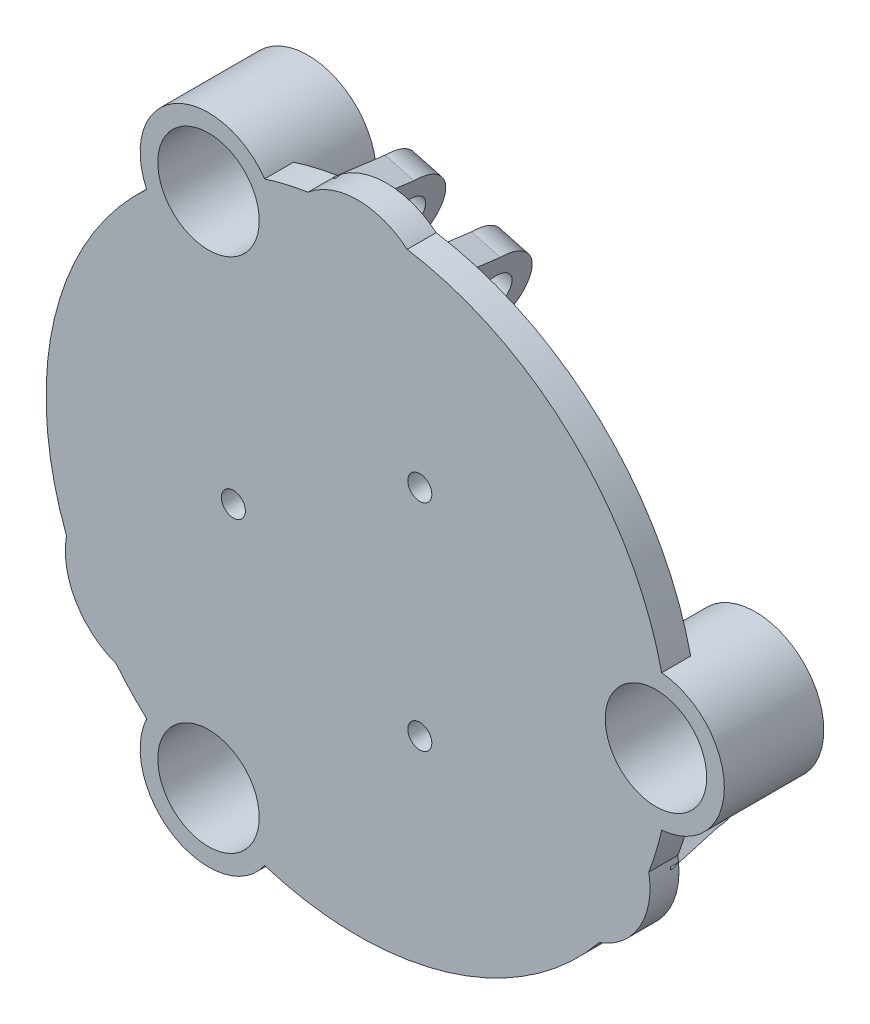
SolidWorks part; units mm, degrees
ref_plane "Front Plane" through (0, 0, 0) normal (0, 0, 1) x (1, 0, 0)
ref_plane "Top Plane" through (0, 0, 0) normal (0, 1, 0) x (1, 0, 0)
ref_plane "Right Plane" through (0, 0, 0) normal (1, 0, 0) x (0, 0, -1)
sketch "S01 - Joining centre of floating Y" plane through (0, 0, 0) normal (0, 0, 1) x (1, 0, 0)
  circle A0 centre (0, 0) radius 9
  dimension "D1" = 18
extrude "01 - Joining centre of floating Y" add sketch "S01 - Joining centre of floating Y" along normal blind 3.5 from offset 33.5
sketch "S02 - Floating spoke 1" plane through (0, 0, 0) normal (0, 0, 1) x (1, 0, 0)
  line L0 (4.65, -8.054) -> (-21.3308, -23.054)
  line L1 (-30.6308, -6.946) -> (-4.65, 8.054)
  arc A0 (-21.3308, -23.054) -> (-30.6308, -6.946) centre (-25.9808, -15) cw
  arc A1 (-4.65, 8.054) -> (4.65, -8.054) centre (0, 0) cw
  dimension "D1" = 9.3
  dimension "D2" = 9.3
  dimension "D3" = 4.65
  dimension "D4" = 4.65
  dimension "D5" = 21.3308
  dimension "D6" = 25.9808
  dimension "D7" = 30.6308
  dimension "D8" = 6.946
extrude "02 - Floating spoke 1" add sketch "S02 - Floating spoke 1" along normal blind 3.5 from offset 33.5
sketch "S03 - Floating spoke 2" plane through (0, 0, 0) normal (0, 0, 1) x (1, 0, 0)
  line L0 (4.65, 8.054) -> (30.6308, -6.946)
  line L1 (21.3308, -23.054) -> (-4.65, -8.054)
  arc A0 (30.6308, -6.946) -> (21.3308, -23.054) centre (25.9808, -15) cw
  arc A1 (-4.65, -8.054) -> (4.65, 8.054) centre (0, 0) cw
  dimension "D1" = 9.3
  dimension "D2" = 9.3
  dimension "D3" = 4.65
  dimension "D4" = 21.3308
  dimension "D5" = 25.9808
  dimension "D6" = 30.6308
  dimension "D7" = 4.65
  dimension "D8" = 6.946
extrude "03 - Floating spoke 2" add sketch "S03 - Floating spoke 2" along normal blind 3.5 from offset 33.5
sketch "S04 - Floating spoke 3" plane through (0, 0, 0) normal (0, 0, 1) x (1, 0, 0)
  line L0 (-9.3, 0) -> (-9.3, 30)
  line L1 (9.3, 30) -> (9.3, 0)
  arc A0 (-9.3, 30) -> (9.3, 30) centre (0, 30) cw
  arc A1 (9.3, 0) -> (-9.3, 0) centre (0, 0) cw
  dimension "D1" = 9.3
  dimension "D2" = 30
extrude "04 - Floating spoke 3" add sketch "S04 - Floating spoke 3" along normal blind 3.5 from offset 33.5
sketch "S05 - Moving tendon tie web 1" plane through (0, 0, 0) normal (0, 0, 1) x (1, 0, 0)
  line L0 (25.2997, -21.2631) -> (6.8189, -19.2535)
  line L1 (8.1811, -6.7273) -> (26.6618, -8.7369)
  arc A0 (6.8189, -19.2535) -> (8.1811, -6.7273) centre (7.5, -12.9904) cw
  arc A1 (26.6618, -8.7369) -> (25.2997, -21.2631) centre (25.9808, -15) cw
  dimension "D1" = 6.3
  dimension "D2" = 6.3
  dimension "D3" = 6.8189
  dimension "D4" = 7.5
  dimension "D5" = 8.1811
  dimension "D6" = 25.2997
  dimension "D7" = 25.9808
  dimension "D8" = 26.6618
  dimension "D9" = 6.7273
  dimension "D10" = 8.7369
extrude "05 - Moving tendon tie web 1" add sketch "S05 - Moving tendon tie web 1" along normal blind 3.5 from offset 33.5
sketch "S06 - Tendon anchor base 1" plane through (0, 0, 0) normal (0, 0, 1) x (1, 0, 0)
  circle A0 centre (7.5, -12.9904) radius 4.2
  dimension "D1" = 8.4
  dimension "D2" = 7.5
  dimension "D3" = 12.9904
extrude "06 - Tendon anchor base 1" add sketch "S06 - Tendon anchor base 1" along normal blind 3.7 from offset 29.8
sketch "S07 - Tendon mouth 1" plane through (0, 0, 0) normal (0, 0, 1) x (1, 0, 0)
  circle A0 centre (7.5, -12.9904) radius 3.15
  dimension "D1" = 6.3
  dimension "D2" = 7.5
  dimension "D3" = 12.9904
extrude "07 - Tendon mouth 1" add sketch "S07 - Tendon mouth 1" along normal blind 1.8 from offset 28
sketch "S08 - Moving tendon tie web 2" plane through (0, 0, 0) normal (0, 0, 1) x (1, 0, 0)
  line L0 (5.7645, 32.5417) -> (13.2645, 15.5321)
  line L1 (1.7355, 10.4487) -> (-5.7645, 27.4583)
  arc A0 (13.2645, 15.5321) -> (1.7355, 10.4487) centre (7.5, 12.9904) cw
  arc A1 (-5.7645, 27.4583) -> (5.7645, 32.5417) centre (0, 30) cw
  dimension "D1" = 6.3
  dimension "D2" = 6.3
  dimension "D3" = 1.7355
  dimension "D4" = 5.7645
  dimension "D5" = 7.5
  dimension "D6" = 13.2645
  dimension "D7" = 5.7645
  dimension "D8" = 10.4487
  dimension "D9" = 27.4583
extrude "08 - Moving tendon tie web 2" add sketch "S08 - Moving tendon tie web 2" along normal blind 3.5 from offset 33.5
sketch "S09 - Tendon anchor base 2" plane through (0, 0, 0) normal (0, 0, 1) x (1, 0, 0)
  circle A0 centre (7.5, 12.9904) radius 4.2
  dimension "D1" = 8.4
  dimension "D2" = 7.5
  dimension "D3" = 12.9904
extrude "09 - Tendon anchor base 2" add sketch "S09 - Tendon anchor base 2" along normal blind 3.7 from offset 29.8
sketch "S10 - Tendon mouth 2" plane through (0, 0, 0) normal (0, 0, 1) x (1, 0, 0)
  circle A0 centre (7.5, 12.9904) radius 3.15
  dimension "D1" = 6.3
  dimension "D2" = 7.5
  dimension "D3" = 12.9904
extrude "10 - Tendon mouth 2" add sketch "S10 - Tendon mouth 2" along normal blind 1.8 from offset 28
sketch "S11 - Moving tendon tie web 3" plane through (0, 0, 0) normal (0, 0, 1) x (1, 0, 0)
  line L0 (-31.0642, -11.2786) -> (-20.0835, 3.7214)
  line L1 (-9.9165, -3.7214) -> (-20.8973, -18.7214)
  arc A0 (-20.0835, 3.7214) -> (-9.9165, -3.7214) centre (-15, 0) cw
  arc A1 (-20.8973, -18.7214) -> (-31.0642, -11.2786) centre (-25.9808, -15) cw
  dimension "D1" = 6.3
  dimension "D2" = 6.3
  dimension "D3" = 9.9165
  dimension "D4" = 15
  dimension "D5" = 20.0835
  dimension "D6" = 20.8973
  dimension "D7" = 25.9808
  dimension "D8" = 31.0642
  dimension "D9" = 11.2786
extrude "11 - Moving tendon tie web 3" add sketch "S11 - Moving tendon tie web 3" along normal blind 3.5 from offset 33.5
sketch "S12 - Tendon anchor base 3" plane through (0, 0, 0) normal (0, 0, 1) x (1, 0, 0)
  circle A0 centre (-15, 0) radius 4.2
  dimension "D1" = 8.4
  dimension "D2" = 15
extrude "12 - Tendon anchor base 3" add sketch "S12 - Tendon anchor base 3" along normal blind 3.7 from offset 29.8
sketch "S13 - Tendon mouth 3" plane through (0, 0, 0) normal (0, 0, 1) x (1, 0, 0)
  circle A0 centre (-15, 0) radius 3.15
  dimension "D1" = 6.3
  dimension "D2" = 15
extrude "13 - Tendon mouth 3" add sketch "S13 - Tendon mouth 3" along normal blind 1.8 from offset 28
sketch "S14 - Joined drive hoop" plane through (0, 0, 0) normal (0, 0, 1) x (1, 0, 0)
  circle A0 centre (0, 0) radius 37.6
  dimension "D2" = 75.2
extrude "14 - Joined drive hoop" add sketch "S14 - Joined drive hoop" along normal blind 3.5 from offset 33.5
sketch "S15 - Sliding guide barrel 1" plane through (0, 0, 0) normal (0, 0, 1) x (1, 0, 0)
  circle A0 centre (36, 0) radius 8.25
  dimension "D1" = 16.5
  dimension "D2" = 36
extrude "15 - Sliding guide barrel 1" add sketch "S15 - Sliding guide barrel 1" along normal blind 12 from offset 25
sketch "S16 - Sliding guide barrel 2" plane through (0, 0, 0) normal (0, 0, 1) x (1, 0, 0)
  circle A0 centre (-18, 31.1769) radius 8.25
  dimension "D1" = 16.5
  dimension "D2" = 18
  dimension "D3" = 31.1769
extrude "16 - Sliding guide barrel 2" add sketch "S16 - Sliding guide barrel 2" along normal blind 12 from offset 25
sketch "S17 - Sliding guide barrel 3" plane through (0, 0, 0) normal (0, 0, 1) x (1, 0, 0)
  circle A0 centre (-18, -31.1769) radius 8.25
  dimension "D1" = 16.5
  dimension "D2" = 18
  dimension "D3" = 31.1769
extrude "17 - Sliding guide barrel 3" add sketch "S17 - Sliding guide barrel 3" along normal blind 12 from offset 25
sketch "S18 - Guide bushing seats" plane through (0, 0, 0) normal (0, 0, 1) x (1, 0, 0)
  circle A0 centre (36, 0) radius 6.12
  circle A1 centre (-18, 31.1769) radius 6.12
  circle A2 centre (-18, -31.1769) radius 6.12
  dimension "D1" = 12.24
  dimension "D2" = 12.24
  dimension "D3" = 12.24
  dimension "D4" = 36
  dimension "D5" = 18
  dimension "D6" = 31.1769
  dimension "D7" = 31.1769
extrude "18 - Guide bushing seats" cut sketch "S18 - Guide bushing seats" along normal blind 14 from offset 24
sketch "S19 - Through tendon tie eyes" plane through (0, 0, 0) normal (0, 0, 1) x (1, 0, 0)
  circle A0 centre (7.5, -12.9904) radius 1.45
  circle A1 centre (7.5, 12.9904) radius 1.45
  circle A2 centre (-15, 0) radius 1.45
  dimension "D1" = 2.9
  dimension "D2" = 2.9
  dimension "D3" = 2.9
  dimension "D4" = 7.5
  dimension "D5" = 15
  dimension "D6" = 12.9904
  dimension "D7" = 12.9904
extrude "19 - Through tendon tie eyes" cut sketch "S19 - Through tendon tie eyes" along normal blind 10 from offset 27.8
sketch3d "Plane points - Integral B1 fork cheek L"
  point P0 (-25.9808, -15, 28)
  point P1 (-8.5941, -10.3413, 28)
  point P2 (-25.9808, -15, 10)
ref_plane "Drilling plane - Integral B1 fork cheek L" through (2.0096, -7.5, 0) normal (-0.2588, 0.9659, 0) x (0.9659, 0.2588, 0)
sketch "S20 - Integral B1 fork cheek L" plane through (2.0096, -7.5, 0) normal (-0.2588, 0.9659, 0) x (0.9659, 0.2588, 0)
  line L0 (-35.0778, -34.5) -> (-22.8778, -34.5)
  line L1 (-22.8778, -34.5) -> (-24.0278, -28)
  line L2 (-33.9278, -28) -> (-35.0778, -34.5)
  arc A0 (-24.0278, -28) -> (-33.9278, -28) centre (-28.9778, -28) ccw
  dimension "D1" = 4.95
  dimension "D2" = 22.8778
  dimension "D3" = 28.9778
  dimension "D4" = 35.0778
  dimension "D5" = 28
  dimension "D6" = 34.5
extrude "20 - Integral B1 fork cheek L" add sketch "S20 - Integral B1 fork cheek L" along normal blind 3.6 from offset 7.2 offset against normal yes
sketch3d "Plane points - Integral B1 fork cheek R"
  point P0 (-25.9808, -15, 28)
  point P1 (-8.5941, -10.3413, 28)
  point P2 (-25.9808, -15, 10)
ref_plane "Drilling plane - Integral B1 fork cheek R" through (2.0096, -7.5, 0) normal (-0.2588, 0.9659, 0) x (0.9659, 0.2588, 0)
sketch "S21 - Integral B1 fork cheek R" plane through (2.0096, -7.5, 0) normal (-0.2588, 0.9659, 0) x (0.9659, 0.2588, 0)
  line L0 (-35.0778, -34.5) -> (-22.8778, -34.5)
  line L1 (-22.8778, -34.5) -> (-24.0278, -28)
  line L2 (-33.9278, -28) -> (-35.0778, -34.5)
  arc A0 (-24.0278, -28) -> (-33.9278, -28) centre (-28.9778, -28) ccw
  dimension "D1" = 4.95
  dimension "D2" = 22.8778
  dimension "D3" = 28.9778
  dimension "D4" = 35.0778
  dimension "D5" = 28
  dimension "D6" = 34.5
extrude "21 - Integral B1 fork cheek R" add sketch "S21 - Integral B1 fork cheek R" along normal blind 3.6 from offset 3.6
sketch3d "Plane points - B1 pivot through both cheeks"
  point P0 (-25.9808, -15, 28)
  point P1 (-8.5941, -10.3413, 28)
  point P2 (-25.9808, -15, 10)
ref_plane "Drilling plane - B1 pivot through both cheeks" through (2.0096, -7.5, 0) normal (-0.2588, 0.9659, 0) x (0.9659, 0.2588, 0)
sketch "S22 - B1 pivot through both cheeks" plane through (2.0096, -7.5, 0) normal (-0.2588, 0.9659, 0) x (0.9659, 0.2588, 0)
  circle A0 centre (-28.9778, -28) radius 1.65
  dimension "D1" = 3.3
  dimension "D2" = 28.9778
  dimension "D3" = 28
extrude "22 - B1 pivot through both cheeks" cut sketch "S22 - B1 pivot through both cheeks" along normal blind 15 from offset 7.5 offset against normal yes
sketch3d "Plane points - B1 recessed pivot screw head"
  point P0 (-25.9808, -15, 28)
  point P1 (-8.5941, -10.3413, 28)
  point P2 (-25.9808, -15, 10)
ref_plane "Drilling plane - B1 recessed pivot screw head" through (2.0096, -7.5, 0) normal (-0.2588, 0.9659, 0) x (0.9659, 0.2588, 0)
sketch "S23 - B1 recessed pivot screw head" plane through (2.0096, -7.5, 0) normal (-0.2588, 0.9659, 0) x (0.9659, 0.2588, 0)
  circle A0 centre (-28.9778, -28) radius 2.7
  dimension "D1" = 5.4
  dimension "D2" = 28.9778
  dimension "D3" = 28
extrude "23 - B1 recessed pivot screw head" cut sketch "S23 - B1 recessed pivot screw head" along normal blind 1.5 from offset 7.3 offset against normal yes
sketch3d "Plane points - Integral B2 fork cheek L"
  point P0 (25.9808, -15, 28)
  point P1 (13.2528, -2.2721, 28)
  point P2 (25.9808, -15, 10)
ref_plane "Drilling plane - Integral B2 fork cheek L" through (5.4904, 5.4904, 0) normal (-0.7071, -0.7071, 0) x (0, 0, 1)
sketch "S24 - Integral B2 fork cheek L" plane through (5.4904, 5.4904, 0) normal (-0.7071, -0.7071, 0) x (0, 0, 1)
  line L0 (34.5, -35.0778) -> (34.5, -22.8778)
  line L1 (34.5, -22.8778) -> (28, -24.0278)
  line L2 (28, -33.9278) -> (34.5, -35.0778)
  arc A0 (28, -24.0278) -> (28, -33.9278) centre (28, -28.9778) ccw
  dimension "D1" = 4.95
  dimension "D2" = 28
  dimension "D3" = 34.5
  dimension "D4" = 22.8778
  dimension "D5" = 28.9778
  dimension "D6" = 35.0778
extrude "24 - Integral B2 fork cheek L" add sketch "S24 - Integral B2 fork cheek L" along normal blind 3.6 from offset 7.2 offset against normal yes
sketch3d "Plane points - Integral B2 fork cheek R"
  point P0 (25.9808, -15, 28)
  point P1 (13.2528, -2.2721, 28)
  point P2 (25.9808, -15, 10)
ref_plane "Drilling plane - Integral B2 fork cheek R" through (5.4904, 5.4904, 0) normal (-0.7071, -0.7071, 0) x (0, 0, 1)
sketch "S25 - Integral B2 fork cheek R" plane through (5.4904, 5.4904, 0) normal (-0.7071, -0.7071, 0) x (0, 0, 1)
  line L0 (34.5, -35.0778) -> (34.5, -22.8778)
  line L1 (34.5, -22.8778) -> (28, -24.0278)
  line L2 (28, -33.9278) -> (34.5, -35.0778)
  arc A0 (28, -24.0278) -> (28, -33.9278) centre (28, -28.9778) ccw
  dimension "D1" = 4.95
  dimension "D2" = 28
  dimension "D3" = 34.5
  dimension "D4" = 22.8778
  dimension "D5" = 28.9778
  dimension "D6" = 35.0778
extrude "25 - Integral B2 fork cheek R" add sketch "S25 - Integral B2 fork cheek R" along normal blind 3.6 from offset 3.6
sketch3d "Plane points - B2 pivot through both cheeks"
  point P0 (25.9808, -15, 28)
  point P1 (13.2528, -2.2721, 28)
  point P2 (25.9808, -15, 10)
ref_plane "Drilling plane - B2 pivot through both cheeks" through (5.4904, 5.4904, 0) normal (-0.7071, -0.7071, 0) x (0, 0, 1)
sketch "S26 - B2 pivot through both cheeks" plane through (5.4904, 5.4904, 0) normal (-0.7071, -0.7071, 0) x (0, 0, 1)
  circle A0 centre (28, -28.9778) radius 2.6
  dimension "D1" = 5.2
  dimension "D2" = 28
  dimension "D3" = 28.9778
extrude "26 - B2 pivot through both cheeks" cut sketch "S26 - B2 pivot through both cheeks" along normal blind 15 from offset 7.5 offset against normal yes
sketch3d "Plane points - B2 recessed pivot screw head"
  point P0 (25.9808, -15, 28)
  point P1 (13.2528, -2.2721, 28)
  point P2 (25.9808, -15, 10)
ref_plane "Drilling plane - B2 recessed pivot screw head" through (5.4904, 5.4904, 0) normal (-0.7071, -0.7071, 0) x (0, 0, 1)
sketch "S27 - B2 recessed pivot screw head" plane through (5.4904, 5.4904, 0) normal (-0.7071, -0.7071, 0) x (0, 0, 1)
  circle A0 centre (28, -28.9778) radius 2.7
  dimension "D1" = 5.4
  dimension "D2" = 28
  dimension "D3" = 28.9778
extrude "27 - B2 recessed pivot screw head" cut sketch "S27 - B2 recessed pivot screw head" along normal blind 1.5 from offset 7.3 offset against normal yes
sketch3d "Plane points - Integral B3 fork cheek L"
  point P0 (0, 30, 28)
  point P1 (-4.6587, 12.6133, 28)
  point P2 (0, 30, 10)
ref_plane "Drilling plane - Integral B3 fork cheek L" through (-7.5, 2.0096, 0) normal (0.9659, -0.2588, 0) x (0, 0, -1)
sketch "S28 - Integral B3 fork cheek L" plane through (-7.5, 2.0096, 0) normal (0.9659, -0.2588, 0) x (0, 0, -1)
  line L0 (-34.5, 35.0778) -> (-34.5, 22.8778)
  line L1 (-34.5, 22.8778) -> (-28, 24.0278)
  line L2 (-28, 33.9278) -> (-34.5, 35.0778)
  arc A0 (-28, 24.0278) -> (-28, 33.9278) centre (-28, 28.9778) ccw
  dimension "D1" = 4.95
  dimension "D2" = 28
  dimension "D3" = 34.5
  dimension "D4" = 22.8778
  dimension "D5" = 28.9778
  dimension "D6" = 35.0778
extrude "28 - Integral B3 fork cheek L" add sketch "S28 - Integral B3 fork cheek L" along normal blind 3.6 from offset 7.2 offset against normal yes
sketch3d "Plane points - Integral B3 fork cheek R"
  point P0 (0, 30, 28)
  point P1 (-4.6587, 12.6133, 28)
  point P2 (0, 30, 10)
ref_plane "Drilling plane - Integral B3 fork cheek R" through (-7.5, 2.0096, 0) normal (0.9659, -0.2588, 0) x (0, 0, -1)
sketch "S29 - Integral B3 fork cheek R" plane through (-7.5, 2.0096, 0) normal (0.9659, -0.2588, 0) x (0, 0, -1)
  line L0 (-34.5, 35.0778) -> (-34.5, 22.8778)
  line L1 (-34.5, 22.8778) -> (-28, 24.0278)
  line L2 (-28, 33.9278) -> (-34.5, 35.0778)
  arc A0 (-28, 24.0278) -> (-28, 33.9278) centre (-28, 28.9778) ccw
  dimension "D1" = 4.95
  dimension "D2" = 28
  dimension "D3" = 34.5
  dimension "D4" = 22.8778
  dimension "D5" = 28.9778
  dimension "D6" = 35.0778
extrude "29 - Integral B3 fork cheek R" add sketch "S29 - Integral B3 fork cheek R" along normal blind 3.6 from offset 3.6
sketch3d "Plane points - B3 pivot through both cheeks"
  point P0 (0, 30, 28)
  point P1 (-4.6587, 12.6133, 28)
  point P2 (0, 30, 10)
ref_plane "Drilling plane - B3 pivot through both cheeks" through (-7.5, 2.0096, 0) normal (0.9659, -0.2588, 0) x (0, 0, -1)
sketch "S30 - B3 pivot through both cheeks" plane through (-7.5, 2.0096, 0) normal (0.9659, -0.2588, 0) x (0, 0, -1)
  circle A0 centre (-28, 28.9778) radius 2.6
  dimension "D1" = 5.2
  dimension "D2" = 28
  dimension "D3" = 28.9778
extrude "30 - B3 pivot through both cheeks" cut sketch "S30 - B3 pivot through both cheeks" along normal blind 15 from offset 7.5 offset against normal yes
sketch3d "Plane points - B3 recessed pivot screw head"
  point P0 (0, 30, 28)
  point P1 (-4.6587, 12.6133, 28)
  point P2 (0, 30, 10)
ref_plane "Drilling plane - B3 recessed pivot screw head" through (-7.5, 2.0096, 0) normal (0.9659, -0.2588, 0) x (0, 0, -1)
sketch "S31 - B3 recessed pivot screw head" plane through (-7.5, 2.0096, 0) normal (0.9659, -0.2588, 0) x (0, 0, -1)
  circle A0 centre (-28, 28.9778) radius 2.7
  dimension "D1" = 5.4
  dimension "D2" = 28
  dimension "D3" = 28.9778
extrude "31 - B3 recessed pivot screw head" cut sketch "S31 - B3 recessed pivot screw head" along normal blind 1.5 from offset 7.3 offset against normal yes
sketch "Sketch1" plane through (0.1461, -0.5453, 0) normal (-0.2588, 0.9659, 0) x (0.9659, 0.2588, 0)
  circle A0 centre (-28.9778, -28) radius 2.6
  dimension "D1" = 5.2
extrude "Cut-Extrude1" cut sketch "Sketch1" against normal blind 16 and the other way through all
sketch "Sketch2" plane through (0, 0, 33.5) normal (0, 0, -1) x (-1, 0, 0)
